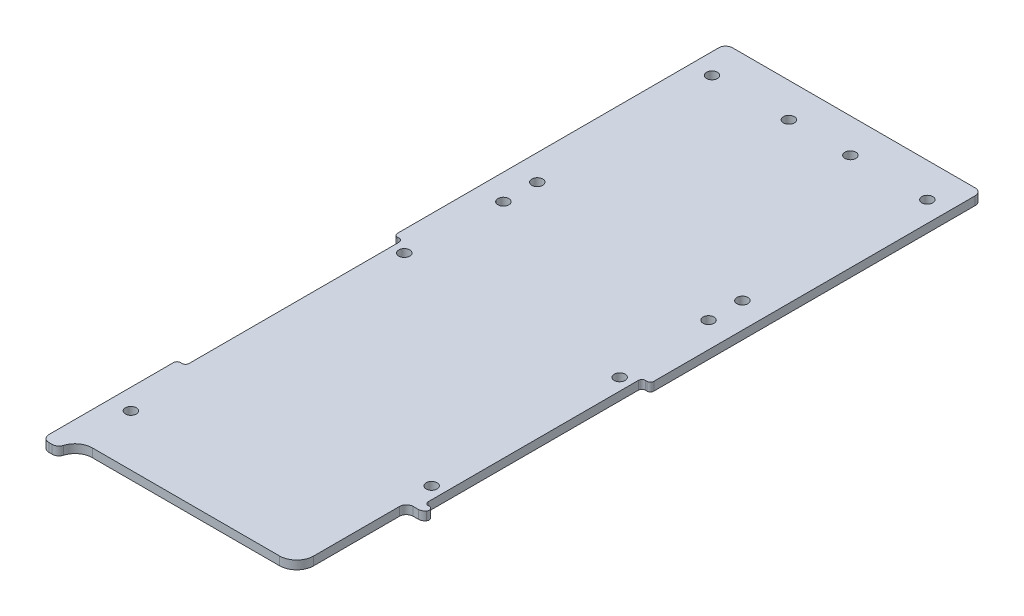
SolidWorks part; units mm, degrees
ref_plane "Front Plane" through (0, 0, 0) normal (0, 0, 1) x (1, 0, 0)
ref_plane "Top Plane" through (0, 0, 0) normal (0, 1, 0) x (1, 0, 0)
ref_plane "Right Plane" through (0, 0, 0) normal (1, 0, 0) x (0, 0, -1)
sketch "Sketch1" plane through (0, 0, 0) normal (0, 1, 0) x (1, 0, 0)
  line L0 (-39.9997, 0) -> (-39.9997, 114.3) construction
  line L1 (-47.625, 127) -> (47.625, 127)
  line L2 (-47.625, 127) -> (-47.625, -127)
  line L3 (-47.625, -127) -> (47.625, -127)
  line L4 (47.625, 127) -> (47.625, -127)
  line L5 (-47.625, 127) -> (47.625, -127) construction
  line L6 (-47.625, -127) -> (47.625, 127) construction
  line L7 (0, 0) -> (0, 127) construction
  line L8 (-39.9997, 0) -> (-39.9997, -101.6) construction
  line L9 (-39.9997, 0) -> (0, 0) construction
  line L10 (-41.275, -127) -> (-41.275, -120.65)
  line L11 (-41.275, -120.65) -> (41.275, -120.65)
  line L12 (41.275, -120.65) -> (41.275, -127)
  line L13 (-39.9997, 114.3) -> (-11.4247, 114.3) construction
  line L14 (39.9997, 114.3) -> (11.4247, 114.3) construction
  circle A0 centre (-39.9997, 114.3) radius 2.032
  circle A1 centre (-39.9997, 0) radius 2.032
  circle A2 centre (-39.9997, -101.6) radius 2.032
  circle A3 centre (39.9997, -101.6) radius 2.032
  circle A4 centre (39.9997, 0) radius 2.032
  circle A5 centre (39.9997, 114.3) radius 2.032
  circle A6 centre (-11.4247, 114.3) radius 2.032
  circle A7 centre (11.4247, 114.3) radius 2.032
  circle A8 centre (-39.9997, -69.85) radius 2.032
  circle A9 centre (39.9997, -69.85) radius 2.032
  point P0 (0, 0)
  dimension "D4" = 4.064
  dimension "D10" = 28.575
  dimension "D1" = 95.25
  dimension "D2" = 254
  dimension "D3" = 7.6253
  dimension "D5" = 12.7
  dimension "D6" = 25.4
  dimension "D7" = 6.35
  dimension "D8" = 6.35
  dimension "D9" = 6.35
  dimension "D11" = 69.85
extrude "Boss-Extrude1" add sketch "Sketch1" along normal blind 3.175 contours L4 L1 L2 L3 A4 A0 A1 A2 A3 A5 | A8 | A3 region at (0, 0, -2.6944) region at (39.9997, 0, 101.6) region at (-39.9997, 0, 69.85)
fillet "Fillet1" radius 2.54 4 edges at (-47.625, 1.5875, -127) (47.625, 1.5875, -127) (47.625, 1.5875, 127) (-47.625, 1.5875, 127)
fillet "Fillet2" radius 2.54 2 edges at (41.275, 1.5875, 127) (-41.275, 1.5875, 127)
fillet "Fillet3" radius 6.35 2 edges at (41.275, 1.5875, 120.65) (-41.275, 1.5875, 120.65)
sketch "Sketch2" plane through (0, 0, 0) normal (0, -1, 0) x (1, 0, 0)
  line L1 (43.815, 127) -> (45.085, 127) construction
  line L2 (40.6451, 123.5787) -> (40.6451, 79.8881)
  line L3 (40.6451, 79.8881) -> (47.625, 79.8881)
  line L11 (47.625, -124.46) -> (47.625, 124.46) construction
  line L12 (43.815, 127) -> (45.085, 127)
  line L13 (47.625, 79.8881) -> (47.625, 124.46)
  arc A0 (35.2956, 120.65) -> (41.3809, 125.1857) centre (35.2956, 127) ccw construction
  arc A1 (43.815, 127) -> (41.3809, 125.1857) centre (43.815, 124.46) ccw construction
  arc A2 (47.625, 124.46) -> (45.085, 127) centre (45.085, 124.46) ccw construction
  arc A3 (40.6451, 123.5787) -> (41.3809, 125.1857) centre (35.2956, 127) ccw
  arc A4 (43.815, 127) -> (41.3809, 125.1857) centre (43.815, 124.46) ccw
  arc A5 (47.625, 124.46) -> (45.085, 127) centre (45.085, 124.46) ccw
  dimension "D2" = 47.1119
  dimension "D1" = 6.9799
extrude "Cut-Extrude1" cut sketch "Sketch2" against normal through all
fillet "Fillet4" radius 6.35 1 edges at (40.6451, 1.5875, 123.5787)
fillet "Fillet5" radius 2.54 2 edges at (47.625, 1.5875, 79.8881) (40.6451, 1.5875, 79.8881)
sketch "Sketch3" plane through (0, 0, 0) normal (0, -1, 0) x (1, 0, 0)
  line L0 (-36.2998, -49.7791) -> (-39.9066, -49.7791) construction
  line L1 (-40.4146, -49.276) -> (-40.4146, -45.7043) construction
  line L2 (-35.7918, -45.7043) -> (-35.7918, -49.276) construction
  line L3 (-39.9066, -45.2013) -> (-36.2998, -45.2013) construction
  line L4 (-36.2998, -37.2027) -> (-39.9066, -37.2027) construction
  line L5 (-35.7918, -33.1279) -> (-35.7918, -36.6996) construction
  line L6 (-40.4146, -36.6996) -> (-40.4146, -33.1279) construction
  line L7 (-39.9066, -32.6249) -> (-36.2998, -32.6249) construction
  line L8 (36.2934, -32.6249) -> (39.9002, -32.6249) construction
  line L9 (40.4082, -33.1279) -> (40.4082, -36.6996) construction
  line L10 (39.9002, -37.2027) -> (36.2934, -37.2027) construction
  line L11 (35.7854, -36.6996) -> (35.7854, -33.1279) construction
  line L12 (36.2934, -45.2013) -> (39.9002, -45.2013) construction
  line L13 (35.7854, -49.276) -> (35.7854, -45.7043) construction
  line L14 (40.4082, -45.7043) -> (40.4082, -49.276) construction
  line L15 (39.9002, -49.7791) -> (36.2934, -49.7791) construction
  line L16 (-36.2998, -49.7791) -> (-39.9066, -49.7791)
  line L17 (-40.4146, -49.276) -> (-40.4146, -45.7043)
  line L18 (-35.7918, -45.7043) -> (-35.7918, -49.276)
  line L19 (-39.9066, -45.2013) -> (-36.2998, -45.2013)
  line L20 (-36.2998, -37.2027) -> (-39.9066, -37.2027)
  line L21 (-35.7918, -33.1279) -> (-35.7918, -36.6996)
  line L22 (-40.4146, -36.6996) -> (-40.4146, -33.1279)
  line L23 (-39.9066, -32.6249) -> (-36.2998, -32.6249)
  line L24 (36.2934, -32.6249) -> (39.9002, -32.6249)
  line L25 (40.4082, -33.1279) -> (40.4082, -36.6996)
  line L26 (39.9002, -37.2027) -> (36.2934, -37.2027)
  line L27 (35.7854, -36.6996) -> (35.7854, -33.1279)
  line L28 (36.2934, -45.2013) -> (39.9002, -45.2013)
  line L29 (35.7854, -49.276) -> (35.7854, -45.7043)
  line L30 (40.4082, -45.7043) -> (40.4082, -49.276)
  line L31 (39.9002, -49.7791) -> (36.2934, -49.7791)
  line L32 (-47.625, -25.836) -> (47.625, -25.836)
  line L33 (-47.625, -124.46) -> (-47.625, 124.46) construction
  line L34 (47.625, -124.46) -> (47.625, 77.3481) construction
  line L35 (0, -25.836) -> (0, -56.0686) construction
  line L1362 (-40.4146, -34.9138) -> (-35.7918, -34.9138)
  line L1857 (-38.1032, -32.6249) -> (-38.1032, -37.2027)
  line L1858 (-38.1032, -45.2013) -> (-38.1032, -49.7791)
  line L1859 (-40.4146, -47.4902) -> (-35.7918, -47.4902)
  circle A0 centre (-38.1032, -34.9138) radius 2.032
  circle A1 centre (-38.1032, -47.4902) radius 2.032
  circle A2 centre (38.1032, -47.4902) radius 2.032
  circle A3 centre (38.1032, -34.9138) radius 2.032
  ellipse E0 centre (-39.9066, -45.7043) end of major axis (-39.3986, -45.7043) minor radius 0.5031 (-39.9066, -45.2013) -> (-40.4146, -45.7043) ccw construction
  ellipse E1 centre (-39.9066, -49.276) end of major axis (-39.3986, -49.276) minor radius 0.5031 (-40.4146, -49.276) -> (-39.9066, -49.7791) ccw construction
  ellipse E6 centre (-36.2998, -49.276) end of major axis (-35.7918, -49.276) minor radius 0.5031 (-36.2998, -49.7791) -> (-35.7918, -49.276) ccw construction
  ellipse E7 centre (-36.2998, -45.7043) end of major axis (-35.7918, -45.7043) minor radius 0.5031 (-35.7918, -45.7043) -> (-36.2998, -45.2013) ccw construction
  ellipse E8 centre (-39.9066, -36.6996) end of major axis (-39.3986, -36.6996) minor radius 0.5031 (-40.4146, -36.6996) -> (-39.9066, -37.2027) ccw construction
  ellipse E9 centre (-36.2998, -36.6996) end of major axis (-35.7918, -36.6996) minor radius 0.5031 (-36.2998, -37.2027) -> (-35.7918, -36.6996) ccw construction
  ellipse E10 centre (-36.2998, -33.1279) end of major axis (-35.7918, -33.1279) minor radius 0.5031 (-35.7918, -33.1279) -> (-36.2998, -32.6249) ccw construction
  ellipse E11 centre (-39.9066, -33.1279) end of major axis (-39.3986, -33.1279) minor radius 0.5031 (-39.9066, -32.6249) -> (-40.4146, -33.1279) ccw construction
  ellipse E12 centre (39.9002, -33.1279) end of major axis (40.4082, -33.1279) minor radius 0.5031 (40.4082, -33.1279) -> (39.9002, -32.6249) ccw construction
  ellipse E13 centre (36.2934, -33.1279) end of major axis (36.8014, -33.1279) minor radius 0.5031 (36.2934, -32.6249) -> (35.7854, -33.1279) ccw construction
  ellipse E14 centre (39.9002, -36.6996) end of major axis (40.4082, -36.6996) minor radius 0.5031 (39.9002, -37.2027) -> (40.4082, -36.6996) ccw construction
  ellipse E15 centre (36.2934, -36.6996) end of major axis (36.8014, -36.6996) minor radius 0.5031 (35.7854, -36.6996) -> (36.2934, -37.2027) ccw construction
  ellipse E16 centre (36.2934, -45.7043) end of major axis (36.8014, -45.7043) minor radius 0.5031 (36.2934, -45.2013) -> (35.7854, -45.7043) ccw construction
  ellipse E17 centre (36.2934, -49.276) end of major axis (36.8014, -49.276) minor radius 0.5031 (35.7854, -49.276) -> (36.2934, -49.7791) ccw construction
  ellipse E18 centre (39.9002, -45.7043) end of major axis (40.4082, -45.7043) minor radius 0.5031 (40.4082, -45.7043) -> (39.9002, -45.2013) ccw construction
  ellipse E19 centre (39.9002, -49.276) end of major axis (40.4082, -49.276) minor radius 0.5031 (39.9002, -49.7791) -> (40.4082, -49.276) ccw construction
  ellipse E20 centre (-39.9066, -45.7043) end of major axis (-39.3986, -45.7043) minor radius 0.5031 (-39.9066, -45.2013) -> (-40.4146, -45.7043) ccw
  ellipse E21 centre (-39.9066, -49.276) end of major axis (-39.3986, -49.276) minor radius 0.5031 (-40.4146, -49.276) -> (-39.9066, -49.7791) ccw
  ellipse E22 centre (-36.2998, -49.276) end of major axis (-35.7918, -49.276) minor radius 0.5031 (-36.2998, -49.7791) -> (-35.7918, -49.276) ccw
  ellipse E23 centre (-36.2998, -45.7043) end of major axis (-35.7918, -45.7043) minor radius 0.5031 (-35.7918, -45.7043) -> (-36.2998, -45.2013) ccw
  ellipse E24 centre (-39.9066, -36.6996) end of major axis (-39.3986, -36.6996) minor radius 0.5031 (-40.4146, -36.6996) -> (-39.9066, -37.2027) ccw
  ellipse E25 centre (-36.2998, -36.6996) end of major axis (-35.7918, -36.6996) minor radius 0.5031 (-36.2998, -37.2027) -> (-35.7918, -36.6996) ccw
  ellipse E26 centre (-36.2998, -33.1279) end of major axis (-35.7918, -33.1279) minor radius 0.5031 (-35.7918, -33.1279) -> (-36.2998, -32.6249) ccw
  ellipse E27 centre (-39.9066, -33.1279) end of major axis (-39.3986, -33.1279) minor radius 0.5031 (-39.9066, -32.6249) -> (-40.4146, -33.1279) ccw
  ellipse E28 centre (39.9002, -33.1279) end of major axis (40.4082, -33.1279) minor radius 0.5031 (40.4082, -33.1279) -> (39.9002, -32.6249) ccw
  ellipse E29 centre (36.2934, -33.1279) end of major axis (36.8014, -33.1279) minor radius 0.5031 (36.2934, -32.6249) -> (35.7854, -33.1279) ccw
  ellipse E30 centre (39.9002, -36.6996) end of major axis (40.4082, -36.6996) minor radius 0.5031 (39.9002, -37.2027) -> (40.4082, -36.6996) ccw
  ellipse E31 centre (36.2934, -36.6996) end of major axis (36.8014, -36.6996) minor radius 0.5031 (35.7854, -36.6996) -> (36.2934, -37.2027) ccw
  ellipse E32 centre (36.2934, -45.7043) end of major axis (36.8014, -45.7043) minor radius 0.5031 (36.2934, -45.2013) -> (35.7854, -45.7043) ccw
  ellipse E33 centre (36.2934, -49.276) end of major axis (36.8014, -49.276) minor radius 0.5031 (35.7854, -49.276) -> (36.2934, -49.7791) ccw
  ellipse E34 centre (39.9002, -45.7043) end of major axis (40.4082, -45.7043) minor radius 0.5031 (40.4082, -45.7043) -> (39.9002, -45.2013) ccw
  ellipse E35 centre (39.9002, -49.276) end of major axis (40.4082, -49.276) minor radius 0.5031 (39.9002, -49.7791) -> (40.4082, -49.276) ccw
  dimension "D2" = 4.064
extrude "Cut-Extrude2" cut sketch "Sketch3" against normal through all contours A0 | A1 | A2 | A3
sketch "Sketch4" plane through (0, 3.175, 0) normal (0, 1, 0) x (1, 0, 0)
  line L11 (-47.625, 124.46) -> (-47.625, -124.46) construction
  line L12 (-47.625, -76.835) -> (-44.45, -76.835)
  line L13 (-47.625, -76.835) -> (-47.625, 3.81)
  line L15 (-47.625, 3.81) -> (-44.45, 3.81)
  line L16 (-44.45, -76.835) -> (-44.45, 3.81)
  line L17 (47.625, 124.46) -> (47.625, -77.3481) construction
  line L18 (47.625, -76.835) -> (44.45, -76.835)
  line L19 (47.625, -76.835) -> (47.625, 3.81)
  line L20 (47.625, 3.81) -> (44.45, 3.81)
  line L45 (44.45, -76.835) -> (44.45, 3.81)
  line L47 (43.1851, -79.8881) -> (45.085, -79.8881) construction
  dimension "D1" = 3.175
  dimension "D2" = 80.645
  dimension "D3" = 3.0531
extrude "Cut-Extrude3" cut sketch "Sketch4" against normal through all and the other way through all
fillet "Fillet6" radius 1.27 8 edges at (-44.45, 1.5875, -3.81) (-47.625, 1.5875, -3.81) (-47.625, 1.5875, 76.835) (-44.45, 1.5875, 76.835) (44.45, 1.5875, 76.835) (47.625, 1.5875, 76.835) (44.45, 1.5875, -3.81) (47.625, 1.5875, -3.81)
